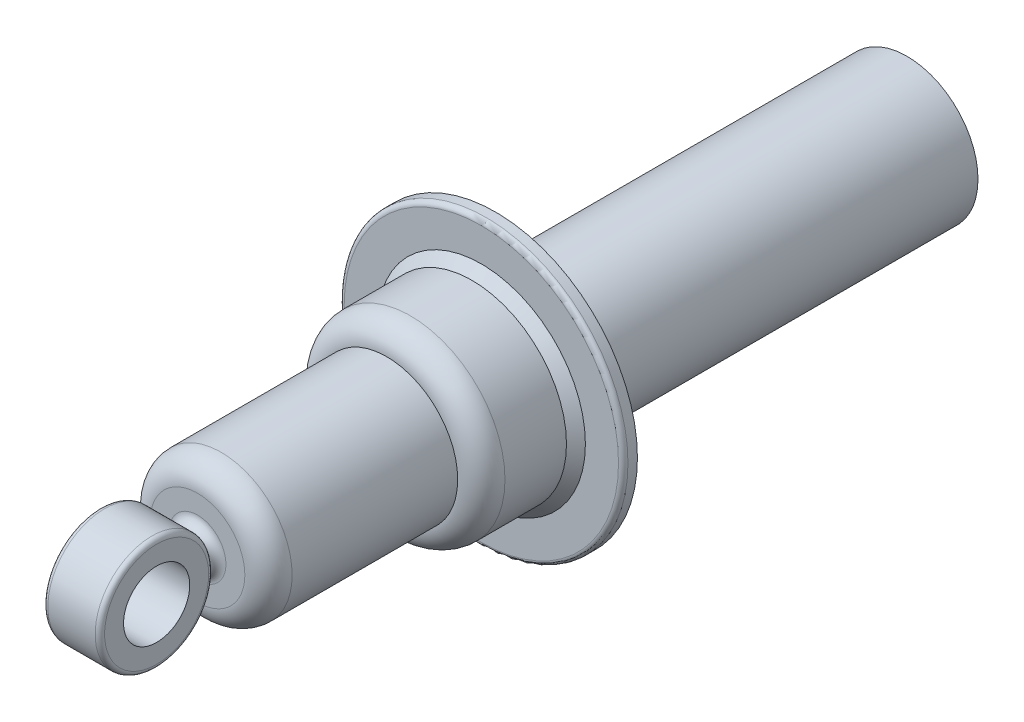
SolidWorks part; units mm, degrees
note: The reader was unsure of these and kept them because the rebuilt part matched: shared geometry of "Sketch2<3>".
material "6061-T6 (SS)"
ref_plane "Front Plane" through (0, 0, 0) normal (1, 0, 0) x (0, 1, 0)
ref_plane "Top Plane" through (0, 0, 0) normal (0, 0, 1) x (0, 1, 0)
ref_plane "Right Plane" through (0, 0, 0) normal (0, 1, 0) x (-1, 0, 0)
sketch "Sketch1" plane through (0, 0, 0) normal (1, 0, 0) x (0, 1, 0)
  line L0 (0, 71.7954) -> (0, -113.1332) construction
  line L1 (-29.7878, 0) -> (45.4037, 0) construction
  line L2 (0, 63) -> (15, 63)
  line L3 (15, 63) -> (15, 23)
  line L4 (15, 23) -> (20, 23)
  line L5 (20, 23) -> (20, 3)
  line L6 (20, 3) -> (30, 3)
  line L7 (30, 3) -> (30, 0)
  line L9 (20, -3) -> (0, -3)
  line L11 (30, 0) -> (0, 0)
  line L12 (15, -3) -> (15, -87)
  line L13 (15, -87) -> (0, -87)
  line L15 (20, -3) -> (20, 0)
  line L16 (20, 0) -> (30, 0)
  line L17 (7.5, -87) -> (7.5, 3)
  line L18 (7.5, 3) -> (0, 3)
  line L19 (0, 3) -> (0, 63)
  dimension "D1" = 110
  dimension "D2" = 3
  dimension "D3" = 87
  dimension "D4" = 20
  dimension "D5" = 40
  dimension "D6" = 30
  dimension "D7" = 60
  dimension "D8" = 150
  dimension "D9" = 30
  dimension "D10" = 15
  dimension "D11" = 90
  dimension "D12" = 60
  dimension "D13" = 40
revolve "Revolve1" add sketch "Sketch1" angle 360 about L0
fillet "Fillet1" radius 1 1 edges at (7.5, 0, -87)
fillet "Fillet2" radius 5 2 edges at (15, 0, 63) (20, 0, 23)
fillet "Fillet3" radius 1 1 edges at (30, 0, 3)
chamfer "Chamfer1" distance 2 angle 45 1 edges at (20, 0, 3)
sketch "Sketch2" plane through (0, 0, 0) normal (1, 0, 0) x (0, 1, 0)
  line L0 (0, 0) -> (0, 100.6741) construction
  line L1 (-10, 63) -> (10, 63)
  line L2 (10, 63) -> (-10, 63) construction
  line L3 (-4, 65) -> (-4, 33.8882)
  line L4 (0, 65.6491) -> (0, 63)
  circle A0 centre (0, 77.6491) radius 7
  arc A1 (5.1429, 66.807) -> (-5.1429, 66.807) centre (0, 77.6491) ccw
  arc A2 (15, 58) -> (10, 63) centre (10, 58) ccw
  arc A3 (-10, 63) -> (-15, 58) centre (-10, 58) ccw
  arc A4 (-10, 63) -> (-15, 58) centre (-10, 58) ccw
  arc A5 (15, 58) -> (10, 63) centre (10, 58) ccw
  arc A6 (-5.1429, 66.807) -> (-6, 63) centre (-6, 65) cw
  arc A7 (5.1429, 66.807) -> (6, 63) centre (6, 65) ccw
  circle A8 centre (0, 77.6491) radius 12
  dimension "D1" = 2
  dimension "D2" = 24
  dimension "D3" = 14
  dimension "D4" = 8
extrude "Boss-Extrude1" add sketch "Sketch2" along normal mid plane 12 contours L0 L1 A7 A1 A0 | L1 L0 A0 A1 A6 L3
revolve "Revolve2" add sketch "Sketch2<3>" angle 360 about L0
sketch "Sketch2<3>" plane through (0, 0, 0) normal (1, 0, 0) x (0, 1, 0) same geometry as "Sketch2"
fillet "Fillet5" radius 1 2 edges at (-6, 0, 65.6491) (6, 0, 65.6491)
